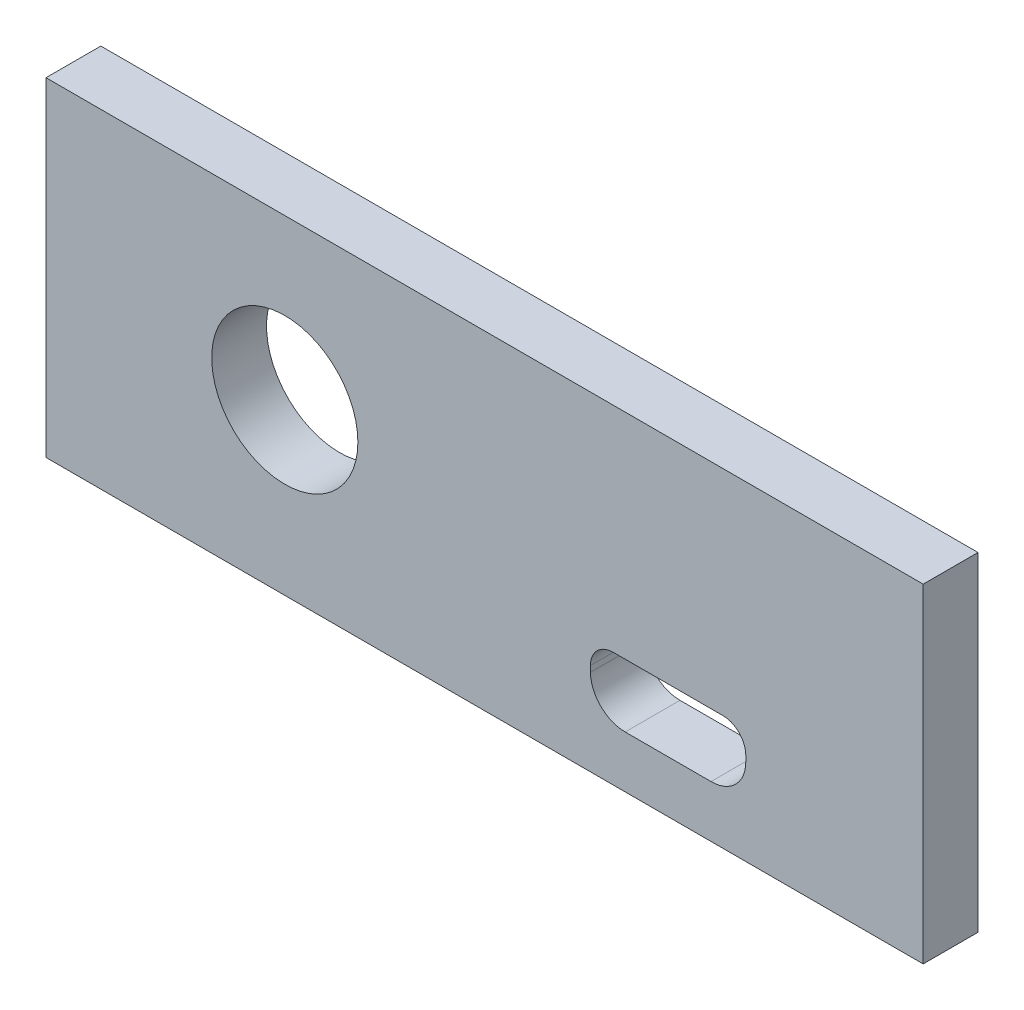
SolidWorks part; units mm, degrees
material "Acrylic (Medium-high impact)"
ref_plane "Front Plane" through (0, 0, 0) normal (0, 0, 1) x (1, 0, 0)
ref_plane "Top Plane" through (0, 0, 0) normal (0, 1, 0) x (1, 0, 0)
ref_plane "Right Plane" through (0, 0, 0) normal (1, 0, 0) x (0, 0, -1)
sketch "Sketch1" plane through (0, 0, 74.2805) normal (0, 0, 1) x (1, 0, 0)
  line L1 (8.9215, 47.1718) -> (56.9215, 47.1718)
  line L2 (8.9215, 47.1718) -> (8.9215, 29.1718)
  line L3 (8.9215, 29.1718) -> (56.9215, 29.1718)
  line L4 (56.9215, 47.1718) -> (56.9215, 29.1718)
  line L33 (39.9643, 35.4616) -> (45.9643, 35.4616)
  line L34 (47.2143, 34.2116) -> (47.2143, 33.8916)
  line L35 (40.6143, 32.0116) -> (45.3128, 32.0116)
  line L36 (38.7143, 34.2116) -> (38.7143, 33.8902)
  circle A2 centre (21.9884, 38.4368) radius 4
  circle A3 centre (21.9884, 38.4368) radius 4
  arc A7 (45.9643, 35.4616) -> (47.2143, 34.2116) centre (45.9643, 34.2116) cw
  arc A8 (47.2143, 33.8916) -> (45.3128, 32.0116) centre (45.3342, 33.8916) cw
  arc A9 (40.6143, 32.0116) -> (38.7143, 33.8902) centre (40.6143, 33.9118) cw
  arc A10 (39.9643, 35.4616) -> (38.7143, 34.2116) centre (39.9643, 34.2116) ccw
  dimension "D1" = 0.25
extrude "Boss-Extrude1" add sketch "Sketch1" along normal blind 3 from offset 0.25
